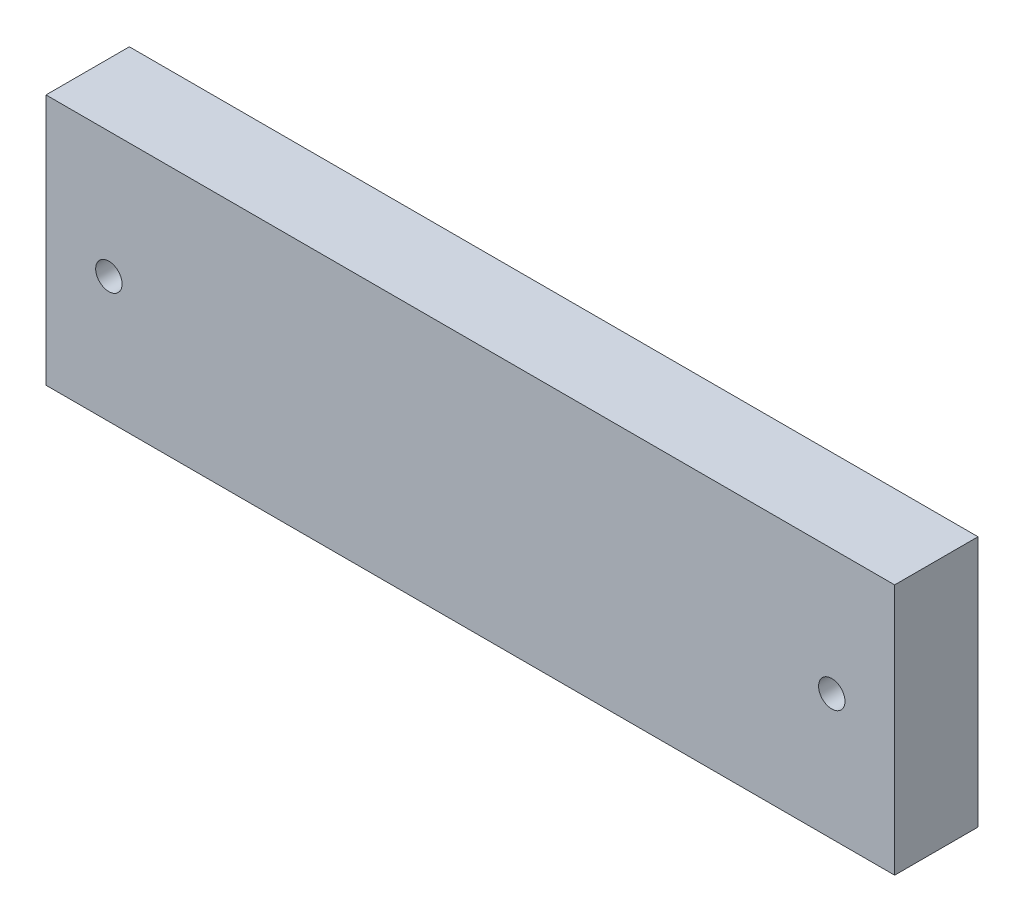
SolidWorks part; units mm, degrees
material "1060 Alloy"
ref_plane "Front Plane" through (0, 0, 0) normal (0, 0, 1) x (1, 0, 0)
ref_plane "Top Plane" through (0, 0, 0) normal (0, 1, 0) x (1, 0, 0)
ref_plane "Right Plane" through (0, 0, 0) normal (1, 0, 0) x (0, 0, -1)
sketch "Sketch1" plane through (0, 0, 0) normal (0, 0, 1) x (1, 0, 0)
  line L1 (-67.5, 20) -> (67.5, 20)
  line L2 (-67.5, 20) -> (-67.5, -20)
  line L3 (-67.5, -20) -> (67.5, -20)
  line L4 (67.5, 20) -> (67.5, -20)
  line L5 (-67.5, 20) -> (67.5, -20) construction
  line L6 (-67.5, -20) -> (67.5, 20) construction
  point P0 (0, 0)
  dimension "D1" = 40
  dimension "D2" = 135
extrude "Boss-Extrude1" add sketch "Sketch1" along normal mid plane 13.26
hole_wizard "M5x0.8 Tapped Hole1" positions "Sketch3" profile "Sketch2" tap size "M5x0.8" standard "ANSI Metric" end condition through all
sketch "Sketch3" plane through (0, 0, 6.63) normal (0, 0, 1) x (1, 0, 0)
  line L0 (-67.5, 20) -> (-67.5, -20) construction
  line L2 (67.5, -20) -> (67.5, 20) construction
  line L3 (67.5, 20) -> (-67.5, 20) construction
  point P0 (57.5, 0)
  point P2 (-57.5, 0)
  point P11 (67.5, 0)
  dimension "D1" = 10
  dimension "D2" = 10
  dimension "D3" = 20
sketch "Sketch2" plane through (57.5, 0, 6.63) normal (1, 0, 0) x (0, -1, 0)
  line L0 (0, 0) -> (0, 13.26)
  line L1 (0, 13.26) -> (2.1, 13.26)
  line L2 (2.1, 13.26) -> (2.1, 0)
  line L5 (2.1, 0) -> (0, 0)
  line L11 (0, -6.35) -> (0, 107.95) construction
  dimension "Thru Tap Drill Dia." = 4.2
  dimension "Thru Tap Drill Depth" = 13.26
cosmetic thread "Hole Thread1" parameters "D2"=5
cosmetic thread "Hole Thread2" parameters "D2"=5
ref_point "Point1"
ref_point "Point2"
